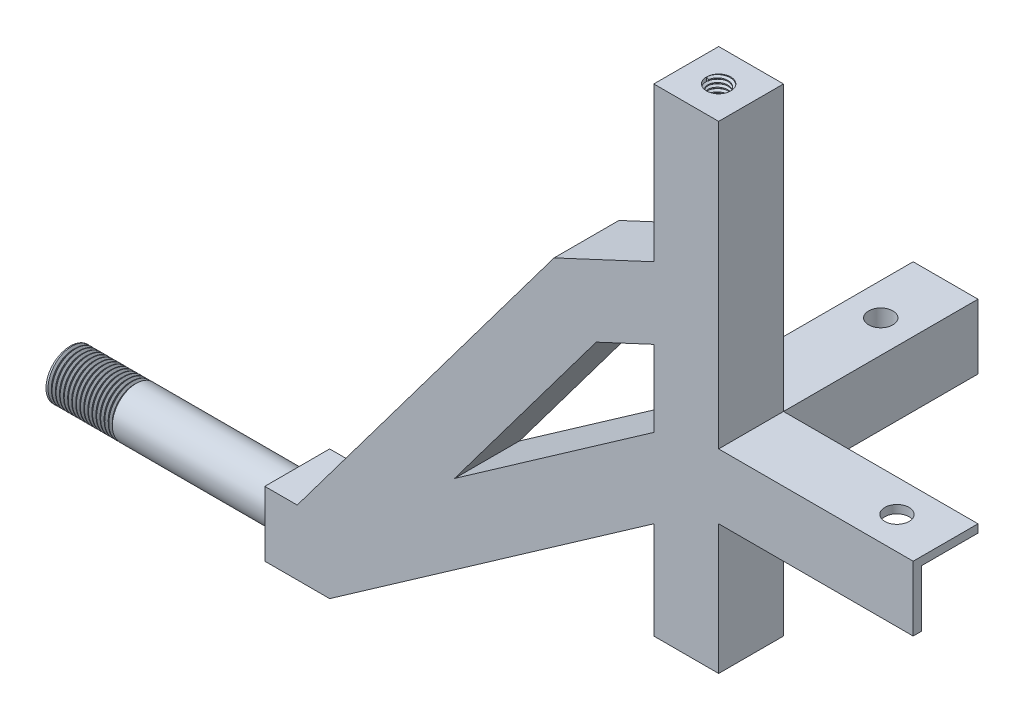
SolidWorks part; units mm, degrees
material "Plain Carbon Steel"
ref_plane "Front Plane" through (0, 0, 0) normal (0, 0, 1) x (1, 0, 0)
ref_plane "Top Plane" through (0, 0, 0) normal (0, 1, 0) x (1, 0, 0)
ref_plane "Right Plane" through (0, 0, 0) normal (1, 0, 0) x (0, 0, -1)
sketch "Sketch1" plane through (0, 0, 0) normal (0, 1, 0) x (1, 0, 0)
  line L1 (12.7, -12.7) -> (-12.7, -12.7)
  line L2 (12.7, -12.7) -> (12.7, 12.7)
  line L3 (12.7, 12.7) -> (-12.7, 12.7)
  line L4 (-12.7, -12.7) -> (-12.7, 12.7)
  line L5 (12.7, -12.7) -> (-12.7, 12.7) construction
  line L6 (12.7, 12.7) -> (-12.7, -12.7) construction
  line L7 (10.16, -10.16) -> (-10.16, -10.16)
  line L8 (10.16, -10.16) -> (10.16, 10.16)
  line L9 (10.16, 10.16) -> (-10.16, 10.16)
  line L10 (-10.16, -10.16) -> (-10.16, 10.16)
  line L11 (10.16, -10.16) -> (-10.16, 10.16) construction
  line L12 (10.16, 10.16) -> (-10.16, -10.16) construction
  point P0 (0, 0)
  point P5 (0, 0)
  dimension "D1" = 2.54
  dimension "1" = 25.4
extrude "Sq_Tb Extrude" add sketch "Sketch1" along normal blind 187.325
sketch "Sketch3" plane through (0, 187.325, 0) normal (0, 1, 0) x (1, 0, 0)
  line L1 (10.16, -10.16) -> (-10.16, -10.16)
  line L2 (10.16, -10.16) -> (10.16, 10.16)
  line L3 (10.16, 10.16) -> (-10.16, 10.16)
  line L4 (-10.16, -10.16) -> (-10.16, 10.16)
  line L5 (10.16, -10.16) -> (-10.16, 10.16) construction
  line L6 (10.16, 10.16) -> (-10.16, -10.16) construction
  circle A0 centre (0, 0) radius 4.7625
  point P0 (0, 0)
  dimension "D1" = 9.525
extrude "End Caps" add sketch "Sketch3" against normal blind 6.35
ref_plane "Mid-Plane" through (0, 93.6625, 0) normal (0, 1, 0) x (1, 0, 0)
mirror "End Cap Mirror" about plane through (0, 93.6625, 0) normal (0, 1, 0) of "End Caps"
thread "Top Thread" pitch 1.5875 method extrude profile "Thread Profile1" start angle 0, offset 0, length 0, pitch 1.5875, diameter 9.525
ref_plane "Plane2" through (-4.7625, 187.325, 0) normal (0, 0, 1) x (-1, 0, 0)
sketch "Thread Profile1" plane through (-4.7625, 187.325, 0) normal (0, 0, 1) x (-1, 0, 0)
  line L0 (0, 0) -> (0, 1.5875) construction
  line L11 (0, 0) -> (0, 1.3891)
  line L12 (0, 1.3891) -> (-0.8593, 0.893)
  line L13 (-0.8593, 0.893) -> (-0.8593, 0.4961)
  line L15 (-0.8593, 0.4961) -> (0, 0)
  line L17 (-0.8593, 0.6945) -> (0, 0.6945) construction
  point P2 (0, 0)
  dimension "Pitch" = 1.5875
  dimension "Profile_Angle" = 60
  dimension "Profile_Land" = 0.3969
  dimension "Profile_Height" = 0.8593
thread "Bottom Thread" pitch 1.5875 method extrude profile "Thread Profile2" start angle 0, offset 0, length 0, pitch 1.5875, diameter 9.525
ref_plane "Plane3" through (4.7625, 0, 0) normal (0, 0, 1) x (1, 0, 0)
sketch "Thread Profile2" plane through (4.7625, 0, 0) normal (0, 0, 1) x (1, 0, 0)
  line L0 (0, 0) -> (0, 1.5875) construction
  line L11 (0, 0) -> (0, 1.3891)
  line L12 (0, 1.3891) -> (-0.8593, 0.893)
  line L13 (-0.8593, 0.893) -> (-0.8593, 0.4961)
  line L15 (-0.8593, 0.4961) -> (0, 0)
  line L17 (-0.8593, 0.6945) -> (0, 0.6945) construction
  point P2 (0, 0)
  dimension "Pitch" = 1.5875
  dimension "Profile_Angle" = 60
  dimension "Profile_Land" = 0.3969
  dimension "Profile_Height" = 0.8593
sketch "Sketch9" plane through (0, 0, 0) normal (0, 0, 1) x (1, 0, 0)
  line L0 (-12.7, 126.996) -> (-51.7653, 108.7796)
  line L1 (-12.7, 187.325) -> (-12.7, 0) construction
  line L2 (-102.0827, 41.6898) -> (-81.7627, 26.4498) construction
  line L3 (-35.2635, 88.4487) -> (-12.7, 98.9702)
  line L4 (-12.7, 38.0909) -> (-139.7, -50.8)
  line L5 (-90.7525, 14.4633) -> (-12.7, 69.0945)
  line L6 (-12.7, 69.0945) -> (-12.7, 38.0909)
  line L8 (-51.7653, 108.7796) -> (-152.4, -25.4)
  line L9 (-12.7, 126.996) -> (-12.7, 98.9702)
  line L10 (-139.7, -50.8) -> (-35.2635, 88.4487)
  line L11 (-139.7, -50.8) -> (-165.1, -50.8)
  line L12 (-165.1, -50.8) -> (-165.1, -25.4)
  line L13 (-165.1, -25.4) -> (-152.4, -25.4)
  line L14 (-32.2327, 117.8878) -> (-21.4982, 94.8676) construction
  line L15 (-165.1, -38.1) -> (0, -38.1) construction
  line L16 (0, -38.1) -> (0, 0) construction
  line L18 (-12.7, 0) -> (12.7, 0) construction
  line L19 (-51.7262, 41.7789) -> (-37.1613, 20.9697) construction
  line L20 (-12.7, 69.0945) -> (32.9312, 3.9003) construction
  line L21 (-139.7, -50.8) -> (-114.9192, -86.2048) construction
  dimension "D3" = 172.7962
  dimension "D1" = 25.4
  dimension "D2" = 43.1038
  dimension "D4" = 65
  dimension "D5" = 12.7
  dimension "D6" = 152.4
  dimension "D7" = 115
  dimension "D8" = 25.4
  dimension "D9" = 50.8
  dimension "D10" = 55.011
  dimension "D11" = 60.329
  dimension "D12" = 38.0909
  dimension "D13" = 88.9052
extrude "Sq_Tb Angles" add sketch "Sketch9" along normal blind 12.7 and the other way blind 12.7 contours L13 L12 L11 L10 L3 L9 L0 L8 | L10 L4 L6 L5 region at (-89.8222, 35.9011, 0) region at (-64.9368, 15.7972, 0)
sketch "Sketch11" plane through (0, 0, 0) normal (0, 0, 1) x (1, 0, 0)
  line L0 (-165.1, -38.1) -> (-254, -38.1)
  line L1 (-165.1, -50.8) -> (-165.1, -25.4) construction
  line L2 (-254, -38.1) -> (-254, -28.575)
  line L3 (-254, -28.575) -> (-165.1, -28.575)
  line L6 (-165.1, -28.575) -> (-165.1, -38.1)
  dimension "D2" = 9.525
  dimension "D4" = 88.9
revolve "Wheel Rod" add sketch "Sketch11" angle 360 about L0
thread "Wheel Threads" pitch 1.5875 method cut profile "Thread Profile3" start angle 0, offset 0, length 25.4, pitch 1.5875, diameter 19.05
ref_plane "Plane4" through (-254, -38.1, -9.525) normal (0, -1, 0) x (0, 0, -1)
sketch "Thread Profile3" plane through (-254, -38.1, -9.525) normal (0, -1, 0) x (0, 0, -1)
  line L0 (0, 0) -> (0, 1.5875) construction
  line L11 (0, 0) -> (0, 1.3891)
  line L12 (0, 1.3891) -> (-0.8593, 0.893)
  line L13 (-0.8593, 0.893) -> (-0.8593, 0.4961)
  line L15 (-0.8593, 0.4961) -> (0, 0)
  line L17 (-0.8593, 0.6945) -> (0, 0.6945) construction
  point P2 (0, 0)
  dimension "Pitch" = 1.5875
  dimension "Profile_Angle" = 60
  dimension "Profile_Land" = 0.3969
  dimension "Profile_Height" = 0.8593
ref_plane "Tie-Rod Mount Plane" through (0, 34.925, 0) normal (0, 1, 0) x (1, 0, 0)
sketch "Sketch15" plane through (0, 34.925, 0) normal (0, 1, 0) x (1, 0, 0)
  line L0 (0, 12.7) -> (12.7, 25.4)
  line L1 (12.7, 12.7) -> (-12.7, 12.7) construction
  line L2 (12.7, 25.4) -> (76.2, 25.4)
  line L3 (0, -12.7) -> (12.7, -25.4)
  line L4 (-12.7, -12.7) -> (12.7, -12.7) construction
  line L5 (0, 12.7) -> (12.7, 12.7)
  line L6 (12.7, -12.7) -> (12.7, 12.7) construction
  line L7 (12.7, 12.7) -> (12.7, -12.7)
  line L8 (12.7, -12.7) -> (0, -12.7)
  line L9 (12.7, -25.4) -> (76.2, -25.4)
  line L10 (76.2, -25.4) -> (76.2, 25.4) construction
  line L11 (12.7, 25.4) -> (12.7, 12.7) construction
  line L12 (12.7, -12.7) -> (12.7, -25.4) construction
  line L13 (76.2, 25.4) -> (88.9, 12.7)
  line L14 (88.9, 12.7) -> (88.9, -12.7)
  line L15 (88.9, -12.7) -> (76.2, -25.4)
  line L16 (12.7, 0) -> (88.9, 0) construction
  dimension "D1" = 12.7
  dimension "D2" = 76.2
  dimension "D3" = 12.7
extrude "Tie-Rod Mount Plate" [suppressed] add sketch "Sketch15" along normal blind 6.35
sketch "Sketch16" [suppressed] plane through (0, 41.275, 0) normal (0, 1, 0) x (1, 0, 0)
  line L0 (12.7, 0) -> (63.5, 0) construction
  line L1 (12.7, -12.7) -> (12.7, 12.7) construction
  line L2 (63.5, 0) -> (63.5, 15.875) construction
  line L3 (12.7, 0) -> (76.2, 0) construction
  circle A0 centre (63.5, 15.875) radius 4.7625
  circle A1 centre (63.5, -15.875) radius 4.7625
  circle A2 centre (76.2, 0) radius 4.7625
  dimension "D1" = 50.8
  dimension "D3" = 9.525
  dimension "D2" = 15.875
  dimension "D4" = 63.5
extrude "Tie-Rod Mount Hole" [suppressed] cut sketch "Sketch16" against normal through all
ref_plane "Plane5" through (0, 50.8, 0) normal (0, -1, 0) x (-1, 0, 0)
sketch "Sketch17" plane through (0, 50.8, 0) normal (0, -1, 0) x (-1, 0, 0)
  line L0 (-12.7, -12.7) -> (-12.7, 12.7) construction
  line L1 (-12.7, 12.7) -> (12.7, 12.7)
  line L2 (-12.7, 12.7) -> (-12.7, 88.9)
  line L3 (-12.7, 88.9) -> (12.7, 88.9)
  line L4 (12.7, 12.7) -> (12.7, 88.9)
  line L5 (-12.7, 12.7) -> (12.7, 88.9) construction
  line L6 (-12.7, 88.9) -> (12.7, 12.7) construction
  line L7 (-12.7, 12.7) -> (12.7, 12.7) construction
  point P4 (0, 50.8)
  dimension "D1" = 25.4
  dimension "D2" = 76.2
extrude "Boss-Extrude1" add sketch "Sketch17" against normal blind 25.4
sketch "Sketch18" plane through (0, 76.2, 0) normal (0, 1, 0) x (1, 0, 0)
  line L0 (0, 0) -> (0, 63.5) construction
  circle A0 centre (0, 63.5) radius 4.7625
  dimension "D1" = 63.5
  dimension "D2" = 9.525
extrude "Cut-Extrude1" cut sketch "Sketch18" against normal through all
sketch "Sketch19" plane through (12.7, 0, 0) normal (1, 0, 0) x (0, 0, -1)
  line L0 (12.7, 76.2) -> (-12.7, 76.2)
  line L1 (-12.7, 187.325) -> (-12.7, 0) construction
  line L2 (-12.7, 76.2) -> (-12.7, 50.8)
  line L3 (-65.0506, 50.8) -> (65.0506, 50.8) construction
  line L4 (-12.7, 50.8) -> (-9.525, 50.8)
  line L5 (-9.525, 50.8) -> (-9.525, 73.025)
  line L6 (-9.525, 73.025) -> (12.7, 73.025)
  line L7 (12.7, 73.025) -> (12.7, 76.2)
  dimension "D1" = 3.175
extrude "Boss-Extrude2" add sketch "Sketch19" along normal blind 76.2
sketch "Sketch20" plane through (0, 76.2, 0) normal (0, 1, 0) x (1, 0, 0)
  line L0 (50.8, -12.7) -> (50.8, 0) construction
  line L2 (88.9, -12.7) -> (12.7, -12.7) construction
  line L3 (0, 0) -> (31.75, 0) construction
  line L4 (31.75, 0) -> (69.85, 0) construction
  circle A0 centre (69.85, 0) radius 4.7625
  circle A1 centre (31.75, 0) radius 4.7625 construction
  point P8 (50.8, 0)
  dimension "D1" = 31.75
  dimension "D2" = 9.525
  dimension "D3" = 69.85
extrude "Cut-Extrude2" cut sketch "Sketch20" against normal through all
